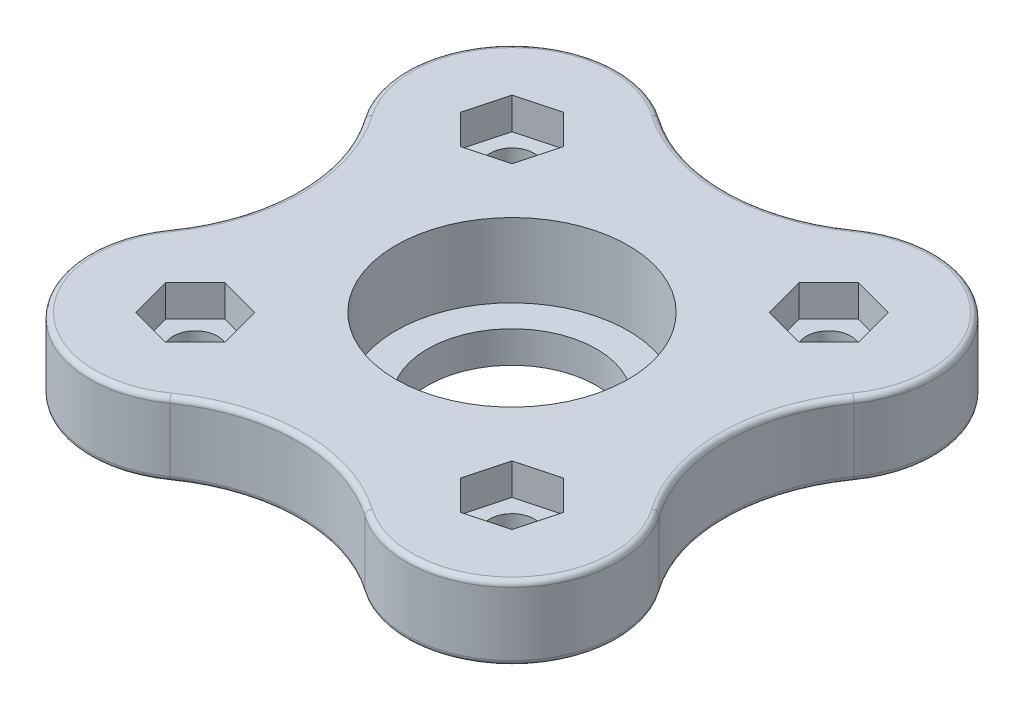
SolidWorks part; units mm, degrees
note: The reader was unsure of these and kept them because the rebuilt part matched: shared geometry of "Sketch1<3>", "Sketch1<4>".
ref_plane "Front Plane" through (0, 0, 0) normal (0, 0, 1) x (1, 0, 0)
ref_plane "Top Plane" through (0, 0, 0) normal (0, 1, 0) x (1, 0, 0)
ref_plane "Right Plane" through (0, 0, 0) normal (1, 0, 0) x (0, 0, -1)
sketch "Sketch1" plane through (0, 0, 0) normal (0, 1, 0) x (1, 0, 0)
  line L1 (-12.1831, 12.1831) -> (-11.152, 16.0311)
  line L2 (-11.152, 16.0311) -> (-13.9689, 18.848)
  line L3 (-13.9689, 18.848) -> (-17.8169, 17.8169)
  line L4 (-17.8169, 17.8169) -> (-18.848, 13.9689)
  line L5 (-15, 15) -> (0, 0) construction
  line L6 (0, 0) -> (15, -15) construction
  line L7 (15, 15) -> (0, 0) construction
  line L8 (0, 0) -> (-15, -15) construction
  line L9 (-18.848, 13.9689) -> (-16.0311, 11.152)
  line L10 (-16.0311, 11.152) -> (-12.1831, 12.1831)
  line L11 (11.152, 16.0311) -> (12.1831, 12.1831)
  line L12 (12.1831, 12.1831) -> (16.0311, 11.152)
  line L13 (16.0311, 11.152) -> (18.848, 13.9689)
  line L14 (18.848, 13.9689) -> (17.8169, 17.8169)
  line L15 (17.8169, 17.8169) -> (13.9689, 18.848)
  line L16 (13.9689, 18.848) -> (11.152, 16.0311)
  line L17 (11.152, -16.0311) -> (13.9689, -18.848)
  line L18 (13.9689, -18.848) -> (17.8169, -17.8169)
  line L19 (17.8169, -17.8169) -> (18.848, -13.9689)
  line L20 (18.848, -13.9689) -> (16.0311, -11.152)
  line L21 (16.0311, -11.152) -> (12.1831, -12.1831)
  line L22 (12.1831, -12.1831) -> (11.152, -16.0311)
  line L23 (-11.152, -16.0311) -> (-12.1831, -12.1831)
  line L24 (-12.1831, -12.1831) -> (-16.0311, -11.152)
  line L25 (-16.0311, -11.152) -> (-18.848, -13.9689)
  line L26 (-18.848, -13.9689) -> (-17.8169, -17.8169)
  line L27 (-17.8169, -17.8169) -> (-13.9689, -18.848)
  line L28 (-13.9689, -18.848) -> (-11.152, -16.0311)
  circle A0 centre (0, 0) radius 8
  circle A1 centre (-15, 15) radius 3.45 construction
  circle A2 centre (0, 0) radius 11
  circle A3 centre (-15, 15) radius 2.1
  circle A4 centre (15, 15) radius 2.1
  circle A5 centre (15, -15) radius 2.1
  circle A6 centre (-15, -15) radius 2.1
  arc A7 (-23.168, 9.2308) -> (-9.2308, 23.168) centre (-15, 15) cw
  arc A8 (9.2308, 23.168) -> (23.168, 9.2308) centre (15, 15) cw
  arc A9 (23.168, -9.2308) -> (9.2308, -23.168) centre (15, -15) cw
  arc A10 (-9.2308, -23.168) -> (-23.168, -9.2308) centre (-15, -15) cw
  arc A11 (-23.168, 9.2308) -> (-23.168, -9.2308) centre (-36.2368, 0) cw
  arc A12 (-9.2308, 23.168) -> (9.2308, 23.168) centre (0, 36.2368) ccw
  arc A13 (23.168, 9.2308) -> (23.168, -9.2308) centre (36.2368, 0) ccw
  arc A14 (9.2308, -23.168) -> (-9.2308, -23.168) centre (0, -36.2368) ccw
  circle A15 centre (0, 0) radius 13
  circle A16 centre (15, 15) radius 3.45 construction
  circle A17 centre (15, -15) radius 3.45 construction
  circle A18 centre (-15, -15) radius 3.45 construction
  point P2 (18.9837, -15)
  point P54 (-15, -15)
  point P55 (-13.0081, -18.45)
  point P56 (0, 0)
  point P57 (0, 0)
  point P58 (0, 0)
  point P59 (0, 0)
  point P60 (0, 0)
  dimension "D1" = 22
  dimension "D2" = 8
  dimension "D3" = 4.2
  dimension "D5" = 10
  dimension "D6" = 16
  dimension "D7" = 26
  dimension "D4" = 30
  dimension "D8" = 6.9
extrude "Boss-Extrude1" add sketch "Sketch1" along normal blind 7 contours A14 A9 A13 A8 A12 A7 A11 A10 A15 A6 A5 A4 A3 | A15 A2
extrude "Boss-Extrude2" add sketch "Sketch1<3>" against normal blind 3 contours A15 A2 | A2 A0
sketch "Sketch1<3>" plane through (0, 0, 0) normal (0, 1, 0) x (1, 0, 0) same geometry as "Sketch1"
extrude "Boss-Extrude3" add sketch "Sketch1<4>" along normal blind 4 contours L27 L28 L23 L24 L25 L26 A6 | L9 L10 L1 L2 L3 L4 A3 | L15 L16 L11 L12 L13 L14 A4 | L21 L22 L17 L18 L19 L20 A5
sketch "Sketch1<4>" plane through (0, 0, 0) normal (0, 1, 0) x (1, 0, 0) same geometry as "Sketch1"
fillet "Fillet1" radius 0.5 17 edges at (0, 0, -20.2368) (0, 7, -20.2368) (-22.0711, 0, -22.0711) (-22.0711, 7, -22.0711) (-20.2368, 0, 0) (-20.2368, 7, 0) (-22.0711, 0, 22.0711) (-22.0711, 7, 22.0711) (0, 0, 20.2368) (0, 7, 20.2368) (22.0711, 0, 22.0711) (22.0711, 7, 22.0711) (20.2368, 0, 0) (20.2368, 7, 0) (0, -3, 13) (22.0711, 0, -22.0711) (22.0711, 7, -22.0711)
